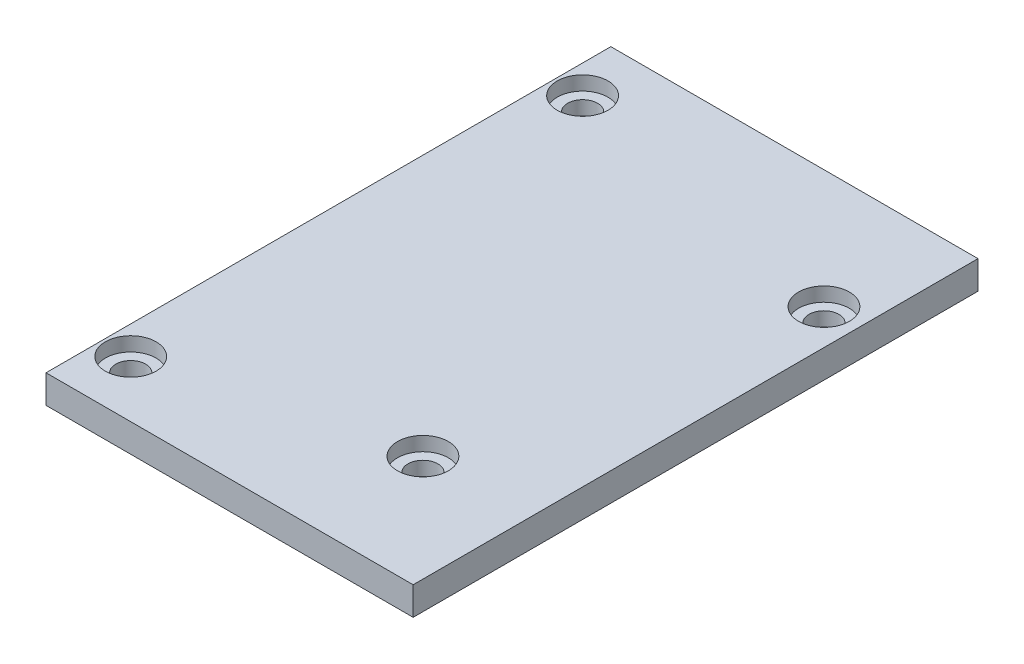
SolidWorks part; units mm, degrees
ref_plane "Front Plane" through (0, 0, 0) normal (0, 0, 1) x (1, 0, 0)
ref_plane "Top Plane" through (0, 0, 0) normal (0, 1, 0) x (1, 0, 0)
ref_plane "Right Plane" through (0, 0, 0) normal (1, 0, 0) x (0, 0, -1)
sketch "Sketch2" plane through (0, 0, 0) normal (0, 1, 0) x (1, 0, 0)
  line L1 (-32.5, 50) -> (32.5, 50)
  line L2 (-32.5, 50) -> (-32.5, -50)
  line L3 (-32.5, -50) -> (32.5, -50)
  line L4 (32.5, 50) -> (32.5, -50)
  line L5 (-32.5, 50) -> (32.5, -50) construction
  line L6 (-32.5, -50) -> (32.5, 50) construction
  circle A0 centre (-27.5, 40) radius 2.65
  circle A1 centre (-27.5, -40) radius 2.65
  circle A2 centre (26.23, 29) radius 2.65
  circle A3 centre (13.65, -29.42) radius 2.65
  point P0 (0, 0)
  dimension "D3" = 5.3
  dimension "D4" = 5
  dimension "D8" = 5.3
  dimension "D9" = 5.3
  dimension "D1" = 65
  dimension "D2" = 100
  dimension "D5" = 5
  dimension "D6" = 10
  dimension "D7" = 10
  dimension "D10" = 18.85
  dimension "D11" = 20.58
  dimension "D12" = 6.27
  dimension "D13" = 21
extrude "Boss-Extrude1" add sketch "Sketch2" along normal blind 5
sketch "Sketch3" plane through (0, 5, 0) normal (0, 1, 0) x (1, 0, 0)
  circle A0 centre (26.23, 29) radius 4.5
  circle A1 centre (13.65, -29.42) radius 4.5
  circle A2 centre (-27.5, 40) radius 4.5
  circle A3 centre (-27.5, -40) radius 4.5
  dimension "D1" = 9
  dimension "D2" = 9
  dimension "D3" = 9
  dimension "D4" = 9
extrude "Cut-Extrude1" cut sketch "Sketch3" against normal blind 2.5
